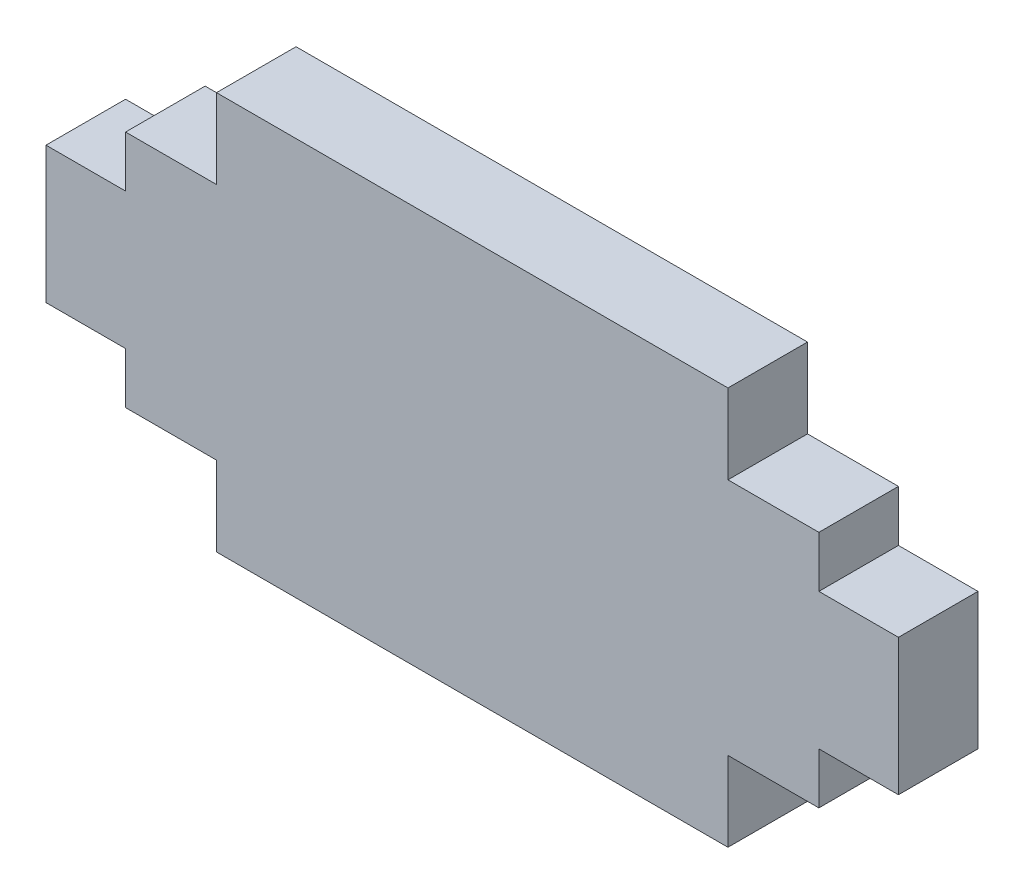
SolidWorks part; units mm, degrees
ref_plane "Ebene vorne (XY)" through (0, 0, 0) normal (0, 0, 1) x (1, 0, 0)
ref_plane "Ebene oben  (XZ)" through (0, 0, 0) normal (0, 1, 0) x (1, 0, 0)
ref_plane "Ebene rechts  (YZ)" through (0, 0, 0) normal (1, 0, 0) x (0, 0, -1)
ref_axis "x-Achse" through (-5.375, 0, 0) along (1, 0, 0)
ref_axis "y-Achse" through (0, 9.625, 0) along (0, -1, 0)
ref_axis "z-Achse" through (0, 0, -0.175) along (0, 0, 1)
sketch "Profile_Laser_profile_3p5" plane through (0, 0, 0) normal (0, 0, 1) x (1, 0, 0)
  line L0 (0, -5.25) -> (4, -5.25)
  line L1 (4, -5.25) -> (4, -8.75)
  line L2 (4, -8.75) -> (26.5, -8.75)
  line L3 (26.5, -8.75) -> (26.5, -5.25)
  line L4 (26.5, -5.25) -> (30.5, -5.25)
  line L5 (30.5, -5.25) -> (30.5, -3)
  line L6 (30.5, -3) -> (34, -3)
  line L7 (34, -3) -> (34, 3)
  line L8 (34, 3) -> (30.5, 3)
  line L9 (30.5, 3) -> (30.5, 5.25)
  line L10 (30.5, 5.25) -> (26.5, 5.25)
  line L11 (26.5, 5.25) -> (26.5, 8.75)
  line L12 (26.5, 8.75) -> (4, 8.75)
  line L13 (4, 8.75) -> (4, 5.25)
  line L14 (4, 5.25) -> (0, 5.25)
  line L15 (0, 5.25) -> (0, 3)
  line L16 (0, 3) -> (-3.5, 3)
  line L17 (-3.5, 3) -> (-3.5, -3)
  line L18 (-3.5, -3) -> (0, -3)
  line L19 (0, -3) -> (0, -5.25)
extrude "Laser_profile_3p5" add sketch "Profile_Laser_profile_3p5" along normal blind 3.5
